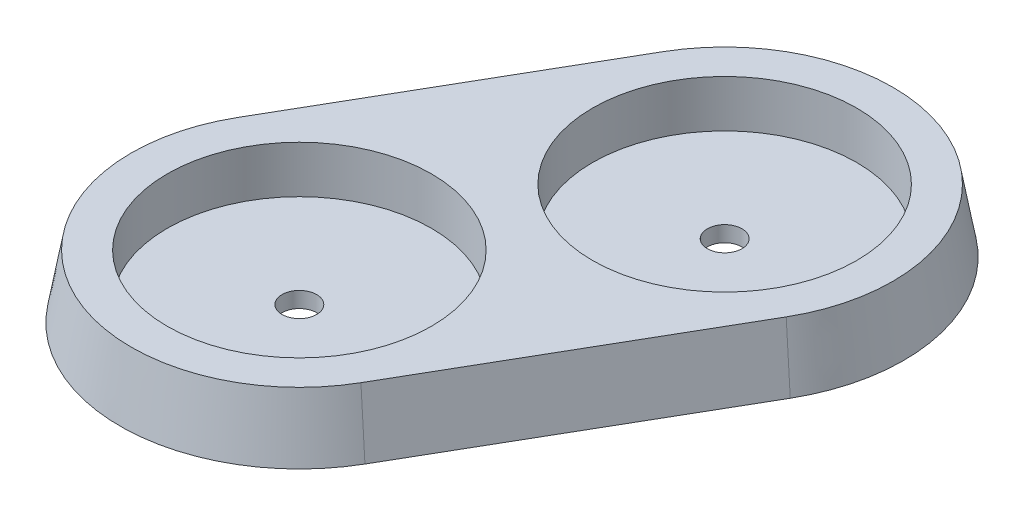
SolidWorks part; units mm, degrees
ref_plane "Front Plane" through (0, 0, 0) normal (0, 0, 1) x (1, 0, 0)
ref_plane "Top Plane" through (0, 0, 0) normal (0, 1, 0) x (1, 0, 0)
ref_plane "Right Plane" through (0, 0, 0) normal (1, 0, 0) x (0, 0, -1)
sketch "Sketch1" plane through (0, 0, 0) normal (0, 1, 0) x (1, 0, 0)
  line L0 (0, 0) -> (-9.9, -17.1473) construction
  line L1 (-9.8727, 5.7) -> (-19.7727, -11.4473)
  line L3 (9.8727, -5.7) -> (-0.0273, -22.8473)
  circle A0 centre (0, 0) radius 8.4
  circle A2 centre (-9.9, -17.1473) radius 8.4
  circle A3 centre (-9.9, -17.1473) radius 1.1
  circle A5 centre (0, 0) radius 1.1
  circle A6 centre (-9.9, -17.1473) radius 11.4
  circle A8 centre (0, 0) radius 11.4
  dimension "D1" = 16.8
  dimension "D4" = 16.8
  dimension "D7" = 2.2
  dimension "D9" = 2.2
  dimension "D10" = 22.8
  dimension "D11" = 22.8
  dimension "D6" = 19.8
extrude "Boss-Extrude1" add sketch "Sketch1" along normal blind 4 draft 10 contours A6 | A8 A6 | A8 | A8 A0 A6 | A8 | A8 A6 | A6 | A8 A6 A0 | A8 A6 A2 | A8 A2 A6 | A6 A8 | A0 A5 | A8 A6 L3 | A2 A3 | A3 | A5 | A8 A6 region at (-13.4272, 0, 3.6794) region at (-4.0812, 0, -7.0689) region at (2.8671, 0, -10.7001) region at (-2.8311, 0, 13.0661) region at (-15.4157, 0, 7.5406) region at (-4.95, 0, 8.5737) region at (3.5272, 0, 13.4679) region at (-9.9, 0, 17.1473) region at (0, 0, 0)
extrude "Cut-Extrude1" cut sketch "Sketch1<3>" against normal blind 4 from surface contours A3 | A5 starting at face at (-4.95, 4, 8.5737)
sketch "Sketch1<3>" plane through (0, 0, 0) normal (0, 1, 0) x (1, 0, 0) same geometry as "Sketch1"
extrude "Cut-Extrude2" cut sketch "Sketch1<4>" against normal blind 3 from surface contours A2 A3 | A0 A5 region at (-4.0812, 0, -7.0689) region at (-2.8311, 0, 13.0661) starting at face at (-9.9, 4, 18.2473)
sketch "Sketch1<4>" plane through (0, 0, 0) normal (0, 1, 0) x (1, 0, 0) same geometry as "Sketch1"
